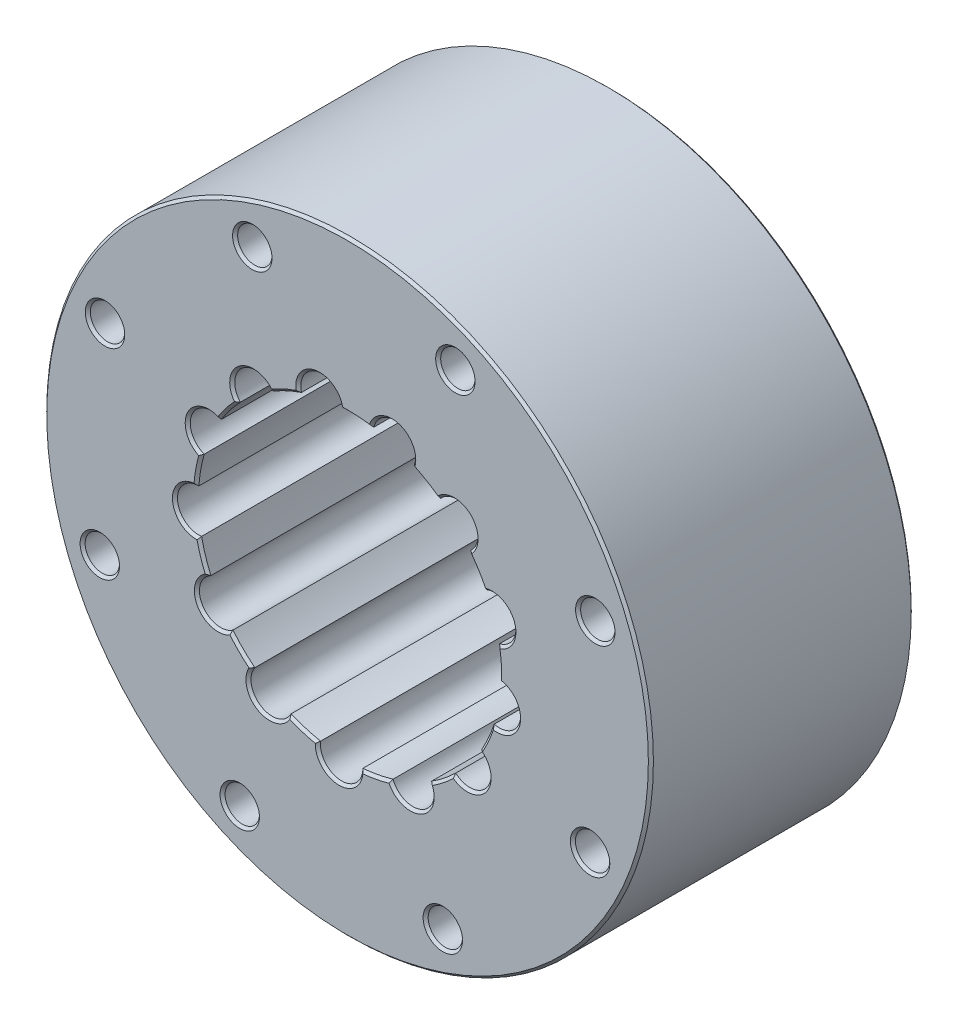
SolidWorks part; units mm, degrees
material "Polylactic Acid (PLA)"
ref_plane "Front Plane" through (0, 0, 0) normal (0, 0, 1) x (1, 0, 0)
ref_plane "Top Plane" through (0, 0, 0) normal (0, 1, 0) x (1, 0, 0)
ref_plane "Right Plane" through (0, 0, 0) normal (1, 0, 0) x (0, 0, -1)
sketch "Sketch2" plane through (0, 0, 0) normal (0, 0, 1) x (1, 0, 0)
  circle A0 centre (0, 0) radius 60
  circle A1 centre (0, 0) radius 45
  dimension "D1" = 120
  dimension "D2" = 15
extrude "Boss-Extrude2" add sketch "Sketch2" along normal mid plane 50
sketch "Sketch3" plane through (0, 0, 25) normal (0, 0, 1) x (1, 0, 0)
  circle A0 centre (0, 0) radius 60
  circle A1 centre (0, 0) radius 60 construction
  arc A2 (29.98, -1.0952) -> (29.5847, 4.9743) centre (0, 0) ccw
  arc A3 (8.504, -28.7695) -> (16.1293, -25.2952) centre (12.4385, -27.2999) ccw
  arc A4 (-5.8399, -29.4261) -> (2.5265, -29.8934) centre (-1.6731, -29.9533) ccw
  arc A5 (-18.846, -23.3416) -> (-11.6551, -27.6434) centre (-15.4015, -25.7448) ccw
  arc A6 (-27.5346, -11.9098) -> (-23.1666, -19.0607) centre (-25.6015, -15.6385) ccw
  arc A7 (-29.9155, 2.2504) -> (-29.3709, -6.1113) centre (-29.9366, -1.9496) ccw
  arc A8 (-25.443, 15.895) -> (-28.8467, 8.2381) centre (-27.4135, 12.186) ccw
  arc A9 (-15.1419, 25.8983) -> (-21.7141, 20.7002) centre (-18.6104, 23.5298) ccw
  arc A10 (-1.3719, 29.9686) -> (-9.607, 28.4202) centre (-5.5438, 29.4833) ccw
  arc A11 (12.7123, 27.1735) -> (4.7009, 29.6294) centre (8.7928, 28.6825) ccw
  arc A12 (23.8843, 18.1532) -> (17.9319, 24.0509) centre (21.115, 21.3109) ccw
  arc A13 (29.5847, 4.9743) -> (27.0549, 12.9627) centre (28.6001, 9.0572) ccw
  arc A14 (28.5076, -9.3442) -> (29.98, -1.0952) centre (29.5332, -5.2714) ccw
  arc A15 (20.8998, -21.5221) -> (26.037, -14.9022) centre (23.7007, -18.3924) ccw
  arc A16 (26.037, -14.9022) -> (28.5076, -9.3442) centre (0, 0) ccw
  arc A17 (16.1293, -25.2952) -> (20.8998, -21.5221) centre (0, 0) ccw
  arc A18 (2.5265, -29.8934) -> (8.504, -28.7695) centre (0, 0) ccw
  arc A19 (-11.6551, -27.6434) -> (-5.8399, -29.4261) centre (0, 0) ccw
  arc A20 (-23.1666, -19.0607) -> (-18.846, -23.3416) centre (0, 0) ccw
  arc A21 (-29.3709, -6.1113) -> (-27.5346, -11.9098) centre (0, 0) ccw
  arc A22 (-28.8467, 8.2381) -> (-29.9155, 2.2504) centre (0, 0) ccw
  arc A23 (-21.7141, 20.7002) -> (-25.443, 15.895) centre (0, 0) ccw
  arc A24 (-9.607, 28.4202) -> (-15.1419, 25.8983) centre (0, 0) ccw
  arc A25 (4.7009, 29.6294) -> (-1.3719, 29.9686) centre (0, 0) ccw
  arc A26 (17.9319, 24.0509) -> (12.7123, 27.1735) centre (0, 0) ccw
  arc A27 (27.0549, 12.9627) -> (23.8843, 18.1532) centre (0, 0) ccw
  point P35 (0, 0)
  dimension "D1" = 60
  dimension "D2" = 8.4
  dimension "D3" = 13
extrude "Boss-Extrude3" add sketch "Sketch3" along normal blind 2
sketch "Sketch4" plane through (0, 0, 25) normal (0, 0, -1) x (-1, 0, 0)
  arc A0 (-12.7123, 27.1735) -> (-17.9319, 24.0509) centre (0, 0) ccw construction
  circle A1 centre (0, 0) radius 45
  circle A2 centre (0, 0) radius 45
  arc A3 (-4.7009, 29.6294) -> (-12.7123, 27.1735) centre (-8.7928, 28.6825) ccw construction
  arc A4 (1.3719, 29.9686) -> (-4.7009, 29.6294) centre (0, 0) ccw construction
  arc A5 (9.607, 28.4202) -> (1.3719, 29.9686) centre (5.5438, 29.4833) ccw construction
  arc A6 (15.1419, 25.8983) -> (9.607, 28.4202) centre (0, 0) ccw construction
  arc A7 (21.7141, 20.7002) -> (15.1419, 25.8983) centre (18.6104, 23.5298) ccw construction
  arc A8 (25.443, 15.895) -> (21.7141, 20.7002) centre (0, 0) ccw construction
  arc A9 (28.8467, 8.2381) -> (25.443, 15.895) centre (27.4135, 12.186) ccw construction
  arc A10 (29.9155, 2.2504) -> (28.8467, 8.2381) centre (0, 0) ccw construction
  arc A11 (29.3709, -6.1113) -> (29.9155, 2.2504) centre (29.9366, -1.9496) ccw construction
  arc A12 (27.5346, -11.9098) -> (29.3709, -6.1113) centre (0, 0) ccw construction
  arc A13 (23.1666, -19.0607) -> (27.5346, -11.9098) centre (25.6015, -15.6385) ccw construction
  arc A14 (18.846, -23.3416) -> (23.1666, -19.0607) centre (0, 0) ccw construction
  arc A15 (11.6551, -27.6434) -> (18.846, -23.3416) centre (15.4015, -25.7448) ccw construction
  arc A16 (5.8399, -29.4261) -> (11.6551, -27.6434) centre (0, 0) ccw construction
  arc A17 (-2.5265, -29.8934) -> (5.8399, -29.4261) centre (1.6731, -29.9533) ccw construction
  arc A18 (-8.504, -28.7695) -> (-2.5265, -29.8934) centre (0, 0) ccw construction
  arc A19 (-16.1293, -25.2952) -> (-8.504, -28.7695) centre (-12.4385, -27.2999) ccw construction
  arc A20 (-20.8998, -21.5221) -> (-16.1293, -25.2952) centre (0, 0) ccw construction
  arc A21 (-26.037, -14.9022) -> (-20.8998, -21.5221) centre (-23.7007, -18.3924) ccw construction
  arc A22 (-28.5076, -9.3442) -> (-26.037, -14.9022) centre (0, 0) ccw construction
  arc A23 (-29.98, -1.0952) -> (-28.5076, -9.3442) centre (-29.5332, -5.2714) ccw construction
  arc A24 (-29.5847, 4.9743) -> (-29.98, -1.0952) centre (0, 0) ccw construction
  arc A25 (-27.0549, 12.9627) -> (-29.5847, 4.9743) centre (-28.6001, 9.0572) ccw construction
  arc A26 (-23.8843, 18.1532) -> (-27.0549, 12.9627) centre (0, 0) ccw construction
  arc A27 (-17.9319, 24.0509) -> (-23.8843, 18.1532) centre (-21.115, 21.3109) ccw construction
  arc A28 (-12.7123, 27.1735) -> (-17.9319, 24.0509) centre (0, 0) ccw
  arc A29 (-4.7009, 29.6294) -> (-12.7123, 27.1735) centre (-8.7928, 28.6825) ccw
  arc A30 (1.3719, 29.9686) -> (-4.7009, 29.6294) centre (0, 0) ccw
  arc A31 (9.607, 28.4202) -> (1.3719, 29.9686) centre (5.5438, 29.4833) ccw
  arc A32 (15.1419, 25.8983) -> (9.607, 28.4202) centre (0, 0) ccw
  arc A33 (21.7141, 20.7002) -> (15.1419, 25.8983) centre (18.6104, 23.5298) ccw
  arc A34 (25.443, 15.895) -> (21.7141, 20.7002) centre (0, 0) ccw
  arc A35 (28.8467, 8.2381) -> (25.443, 15.895) centre (27.4135, 12.186) ccw
  arc A36 (29.9155, 2.2504) -> (28.8467, 8.2381) centre (0, 0) ccw
  arc A37 (29.3709, -6.1113) -> (29.9155, 2.2504) centre (29.9366, -1.9496) ccw
  arc A38 (27.5346, -11.9098) -> (29.3709, -6.1113) centre (0, 0) ccw
  arc A39 (23.1666, -19.0607) -> (27.5346, -11.9098) centre (25.6015, -15.6385) ccw
  arc A40 (18.846, -23.3416) -> (23.1666, -19.0607) centre (0, 0) ccw
  arc A41 (11.6551, -27.6434) -> (18.846, -23.3416) centre (15.4015, -25.7448) ccw
  arc A42 (5.8399, -29.4261) -> (11.6551, -27.6434) centre (0, 0) ccw
  arc A43 (-2.5265, -29.8934) -> (5.8399, -29.4261) centre (1.6731, -29.9533) ccw
  arc A44 (-8.504, -28.7695) -> (-2.5265, -29.8934) centre (0, 0) ccw
  arc A45 (-16.1293, -25.2952) -> (-8.504, -28.7695) centre (-12.4385, -27.2999) ccw
  arc A46 (-20.8998, -21.5221) -> (-16.1293, -25.2952) centre (0, 0) ccw
  arc A47 (-26.037, -14.9022) -> (-20.8998, -21.5221) centre (-23.7007, -18.3924) ccw
  arc A48 (-28.5076, -9.3442) -> (-26.037, -14.9022) centre (0, 0) ccw
  arc A49 (-29.98, -1.0952) -> (-28.5076, -9.3442) centre (-29.5332, -5.2714) ccw
  arc A50 (-29.5847, 4.9743) -> (-29.98, -1.0952) centre (0, 0) ccw
  arc A51 (-27.0549, 12.9627) -> (-29.5847, 4.9743) centre (-28.6001, 9.0572) ccw
  arc A52 (-23.8843, 18.1532) -> (-27.0549, 12.9627) centre (0, 0) ccw
  arc A53 (-17.9319, 24.0509) -> (-23.8843, 18.1532) centre (-21.115, 21.3109) ccw
  dimension "D1" = 0
extrude "Extrude-Thin1" add sketch "Sketch4" along normal up to surface (50 mm away) thin up to face at (60, 0, -25) thin type one direction wall 2
sketch "Sketch5" plane through (0, 0, 27) normal (0, 0, 1) x (1, 0, 0)
  circle A0 centre (0, 0) radius 52.5
  point P3 (49.0019, 18.8432)
  point P4 (47.9737, -21.3254)
  point P8 (18.8432, -49.0019)
  point P9 (-21.3254, -47.9737)
  point P10 (-49.0019, -18.8432)
  point P11 (-47.9737, 21.3254)
  point P12 (-18.8432, 49.0019)
  point P13 (21.3254, 47.9737)
  point P14 (0, 0)
  dimension "D1" = 105
  dimension "D2" = 8
hole_wizard "Ø6.0mm Dowel Hole1" positions "Sketch5" profile "Sketch6" hole size "Ø6.0" standard "ISO" end condition through all
sketch "Sketch6" plane through (21.3254, 47.9737, 27) normal (1, 0, 0) x (0, -1, 0)
  line L0 (0, 0) -> (0, 52)
  line L1 (0, 52) -> (3.4, 52)
  line L2 (3.4, 52) -> (3.4, 0)
  line L5 (3.4, 0) -> (0, 0)
  line L11 (0, -6.35) -> (0, 107.95) construction
  dimension "Thru Hole Dia." = 6.8
  dimension "Thru Hole Depth" = 52
chamfer "Chamfer1" distance 0.5 angle 45 45 edges at (45, 0, -25) (29.9366, 1.9496, 27) (32.6041, 10.3252, 27) (25.6015, 15.6385, 27) (24.0712, 24.2944, 27) (15.4015, 25.7448, 27) (10.0238, 32.6981, 27) (1.6731, 29.9533, 27) (-6.32, 33.611, 27) (-12.4385, 27.2999, 27) (-21.2158, 26.824, 27) (-23.7007, 18.3924, 27) (-31.2514, 13.892, 27) (-29.5332, 5.2714, 27) (-34.1277, -2.2225, 27) (-28.6001, -9.0572, 27) (-29.1857, -17.8279, 27) (-21.115, -21.3109, 27) (-17.5577, -29.3491, 27) (-8.7928, -28.6825, 27) (-1.9073, -34.1468, 27) (5.5438, -29.4833, 27) (14.1799, -31.1219, 27) (18.6104, -23.5298, 27) (27.0188, -20.9673, 27) (27.4135, -12.186, 27) (33.6679, -6.0094, 27) (60, 0, 27) (60, 0, -25) (-45.6019, -18.8432, 27) (-45.6019, -18.8432, -25) (-17.9254, -47.9737, 27) (-17.9254, -47.9737, -25) (22.2432, -49.0019, 27) (22.2432, -49.0019, -25) (51.3737, -21.3254, 27) (51.3737, -21.3254, -25) (52.4019, 18.8432, 27) (52.4019, 18.8432, -25) (24.7254, 47.9737, 27) (24.7254, 47.9737, -25) (-44.5737, 21.3254, 27) (-44.5737, 21.3254, -25) (-15.4432, 49.0019, 27) (-15.4432, 49.0019, -25)
chamfer "Chamfer2" distance 0.5 angle 45 52 edges at (10.61, 34.6102, -25) (1.7846, 31.9502, -25) (-6.6895, 35.5765, -25) (-13.2678, 29.1199, -25) (-22.4565, 28.3927, -25) (-25.2807, 19.6185, -25) (-33.079, 14.7044, -25) (-31.5021, 5.6228, -25) (-36.1235, -2.3525, -25) (-30.5068, -9.661, -25) (-30.8925, -18.8704, -25) (-22.5227, -22.7316, -25) (-18.5844, -31.0654, -25) (-9.379, -30.5947, -25) (-2.0189, -36.1437, -25) (5.9134, -31.4489, -25) (15.0092, -32.9418, -25) (19.8511, -25.0985, -25) (28.5988, -22.1934, -25) (29.2411, -12.9984, -25) (35.6368, -6.3608, -25) (31.9324, 2.0795, -25) (34.5108, 10.929, -25) (27.3083, 16.6811, -25) (25.4788, 25.7152, -25) (16.4282, 27.4611, -25) (15.4015, 25.7448, -25) (24.0712, 24.2944, -25) (25.6015, 15.6385, -25) (32.6041, 10.3252, -25) (29.9366, 1.9496, -25) (33.6679, -6.0094, -25) (27.4135, -12.186, -25) (27.0188, -20.9673, -25) (18.6104, -23.5298, -25) (14.1799, -31.1219, -25) (5.5438, -29.4833, -25) (-1.9073, -34.1468, -25) (-8.7928, -28.6825, -25) (-17.5577, -29.3491, -25) (-21.115, -21.3109, -25) (-29.1857, -17.8279, -25) (-28.6001, -9.0572, -25) (-34.1277, -2.2225, -25) (-29.5332, 5.2714, -25) (-31.2514, 13.892, -25) (-23.7007, 18.3924, -25) (-21.2158, 26.824, -25) (-12.4385, 27.2999, -25) (-6.32, 33.611, -25) (1.6731, 29.9533, -25) (10.0238, 32.6981, -25)
